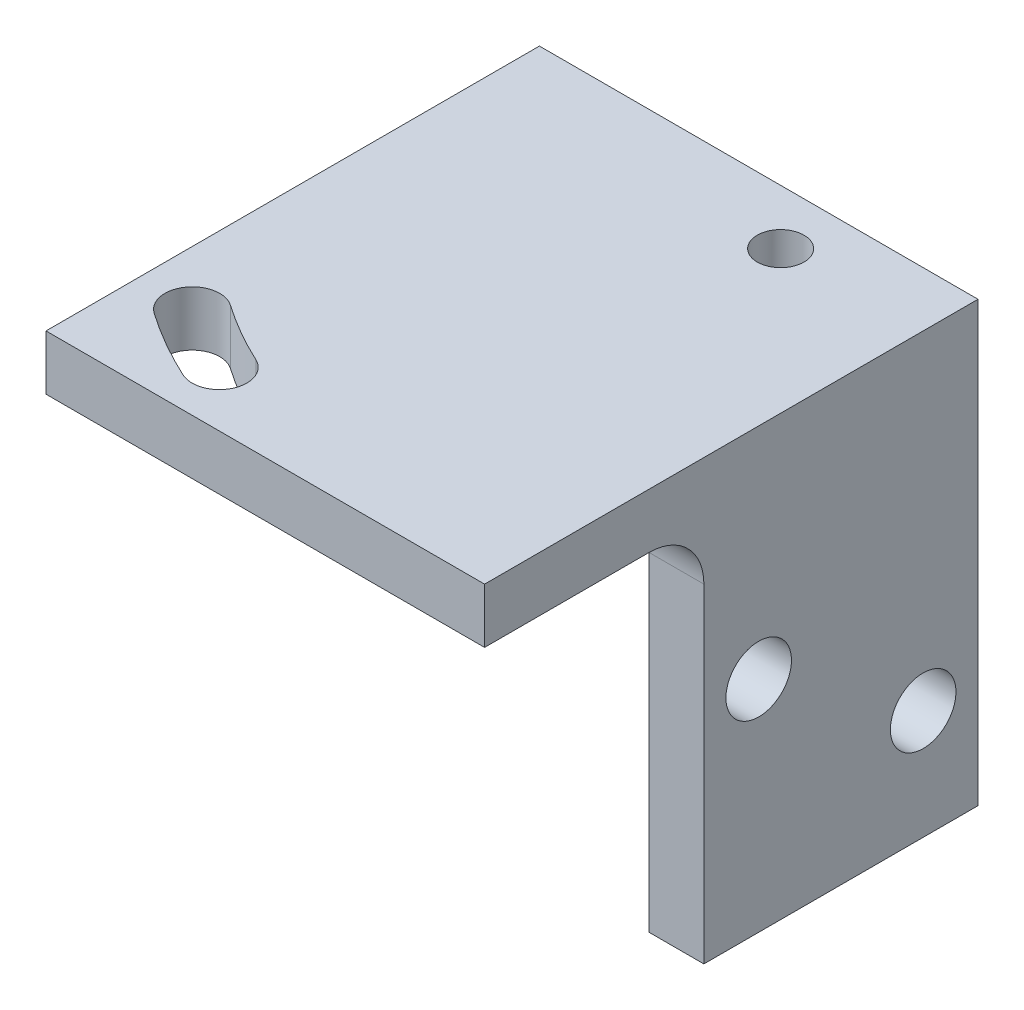
SolidWorks part; units mm, degrees
ref_plane "Front Plane" through (0, 0, 0) normal (0, 0, 1) x (1, 0, 0)
ref_plane "Top Plane" through (0, 0, 0) normal (0, 1, 0) x (1, 0, 0)
ref_plane "Right Plane" through (0, 0, 0) normal (1, 0, 0) x (0, 0, -1)
sketch "Sketch1" plane through (0, 0, 0) normal (0, 0, 1) x (1, 0, 0)
  line L1 (0, 0) -> (-25.4, 0)
  line L2 (0, 0) -> (0, -25.4)
  line L3 (0, -25.4) -> (-25.4, -25.4)
  line L4 (-25.4, 0) -> (-25.4, -25.4)
  line L5 (-25.4, -25.4) -> (-3.175, -25.4)
  line L6 (-25.4, -25.4) -> (-25.4, -3.175)
  line L7 (-25.4, -3.175) -> (-3.175, -3.175)
  line L8 (-3.175, -25.4) -> (-3.175, -3.175)
  dimension "D1" = 3.175
  dimension "D2" = 3.175
  dimension "D3" = 25.4
  dimension "D4" = 25.4
extrude "Boss-Extrude1" add sketch "Sketch1" along normal blind 28.575 contours L8 L3 L2 L1 L4 L7 region at (-0.3592, -12.7, 0)
sketch "Sketch3" plane through (0, 0, 0) normal (0, 1, 0) x (1, 0, 0)
  line L0 (0, -28.575) -> (0, 0) construction
  line L1 (0, 0) -> (-25.4, 0) construction
  point P0 (-18.555, -25.375)
  point P1 (-8.255, -3.175)
  dimension "D1" = 8.255
  dimension "D2" = 10.3
  dimension "D3" = 3.175
  dimension "D4" = 22.2
hole_wizard "#6-32 Tapped Hole1" positions "3DSketch2" profile "Sketch5" tap size "#6-32" standard "ANSI Inch" end condition through all
sketch3d "3DSketch2"
  point P0 (-8.255, 0, 3.175)
  point P3 (-18.555, 0, 25.375)
sketch "Sketch5" plane through (-8.255, 0, 3.175) normal (1, 0, 0) x (0, 0, 1)
  line L0 (0, 0) -> (0, 25.4)
  line L1 (0, 25.4) -> (1.3525, 25.4)
  line L2 (1.3525, 25.4) -> (1.3525, 0)
  line L5 (1.3525, 0) -> (0, 0)
  line L11 (0, -6.35) -> (0, 107.95) construction
  dimension "Thru Tap Drill Dia." = 2.7051
  dimension "Thru Tap Drill Depth" = 25.4
cosmetic thread "Hole Thread1" parameters "D2"=3.5052
cosmetic thread "Hole Thread2" parameters "D2"=3.5052
hole_wizard "#6 Clearance Hole1" positions "3DSketch3" profile "Sketch7" hole size "#6" standard "ANSI Inch" end condition through all
sketch3d "3DSketch3"
  line L0 (-3.175, -25.4, 28.575) -> (-3.175, -25.4, 0) construction
  line L1 (-3.175, -25.4, 0) -> (-3.175, -3.175, 0) construction
  point P0 (-3.175, -12.7, 12.7)
  point P2 (-3.175, -19.05, 3.175)
  dimension "D1" = 6.35
  dimension "D2" = 12.7
  dimension "D3" = 3.175
  dimension "D4" = 12.7
sketch "Sketch7" plane through (-3.175, -12.7, 12.7) normal (0, 1, 0) x (0, 0, 1)
  line L0 (0, 0) -> (0, 3.175)
  line L1 (0, 3.175) -> (1.8986, 3.175)
  line L2 (1.8986, 3.175) -> (1.8986, 0)
  line L5 (1.8986, 0) -> (0, 0)
  line L11 (0, -6.35) -> (0, 107.95) construction
  dimension "Thru Hole Dia." = 3.7973
  dimension "Thru Hole Depth" = 3.175
sketch "Sketch8" plane through (0, 0, 0) normal (0, 1, 0) x (1, 0, 0)
  line L0 (-8.255, -3.175) -> (-22.2535, -23.2492)
  line L1 (-8.255, -3.175) -> (-18.555, -25.375)
  line L2 (-8.255, -3.175) -> (-14.5435, -26.8263)
  arc A0 (-23.5255, -22.2994) -> (-12.9969, -27.1843) centre (-8.255, -3.175) ccw
  circle A1 centre (-14.5435, -26.8263) radius 1.5875
  circle A2 centre (-22.2535, -23.2492) radius 1.5875
  arc A3 (-21.3455, -21.947) -> (-14.1356, -25.2921) centre (-8.255, -3.175) ccw
  arc A4 (-23.1616, -24.5513) -> (-14.9515, -28.3605) centre (-8.255, -3.175) ccw
  circle A5 centre (-18.555, -25.375) radius 1.5875
  circle M2 centre (-18.555, -25.375) radius 1.3525
  dimension "D1" = 3.175
  dimension "D2" = 3.175
  dimension "D3" = 10
  dimension "D4" = 10
extrude "Cut-Extrude1" cut sketch "Sketch8" against normal through all contours A0 A2 | A0 A2 L0 | L0 A2 A0 | A5 A0 A2 A4 | A5 A3 A2 A0 | A5 A0 M2 | A0 A5 L1 M2 | L1 A5 A0 M2 region at (-21.3161, 0, 23.0702) region at (-19.9716, 0, 23.5594) region at (-22.4096, 0, 22.3077) region at (-17.2363, 0, 24.5331) region at (-17.9572, 0, 24.0318) region at (-22.6335, 0, 23.7941) region at (-20.9294, 0, 25.2257) region at (-19.8874, 0, 24.7502)
sketch "Sketch9" plane through (-3.175, 0, 0) normal (-1, 0, 0) x (0, 0, 1)
  line L0 (28.575, -3.175) -> (0, -3.175) construction
  line L1 (28.575, -25.4) -> (15.875, -25.4)
  line L2 (28.575, -25.4) -> (28.575, -3.175)
  line L3 (28.575, -3.175) -> (15.875, -3.175)
  line L4 (15.875, -25.4) -> (15.875, -3.175)
  line L5 (0, -25.4) -> (0, -3.175) construction
  dimension "D1" = 15.875
extrude "Cut-Extrude2" cut sketch "Sketch9" against normal through all
fillet "Fillet1" radius 3.175 2 edges at (-3.175, -3.175, 7.9375) (-1.5875, -3.175, 15.875)
